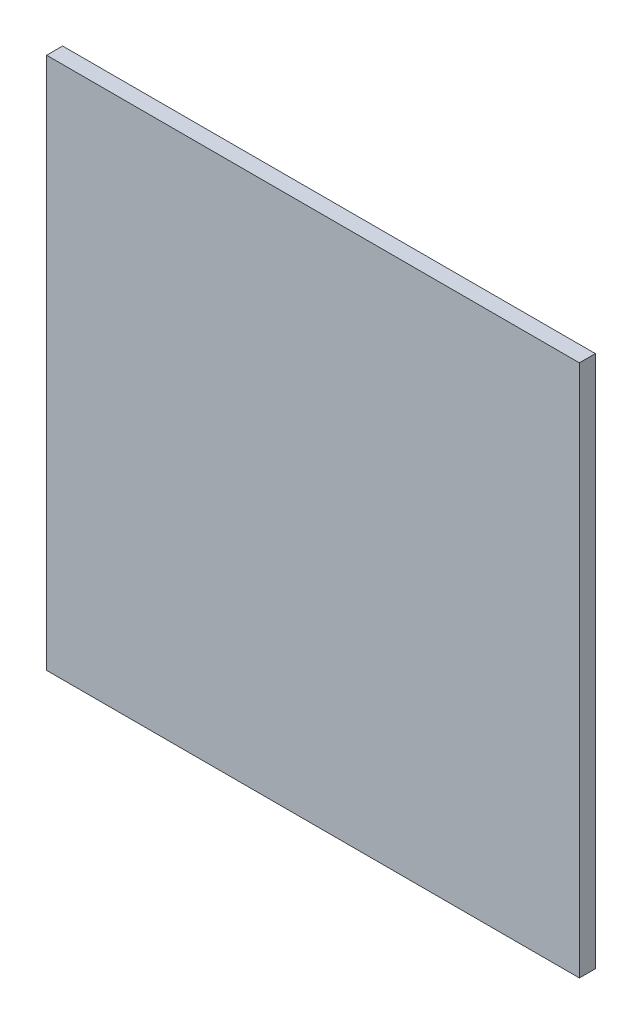
SolidWorks part; units mm, degrees
ref_plane "前视基准面" through (0, 0, 0) normal (0, 0, 1) x (1, 0, 0)
ref_plane "上视基准面" through (0, 0, 0) normal (0, 1, 0) x (1, 0, 0)
ref_plane "右视基准面" through (0, 0, 0) normal (1, 0, 0) x (0, 0, -1)
other "Configuration Table"
sketch "草图2" plane through (0, 0, 0) normal (0, 0, 1) x (1, 0, 0)
  circle A0 centre (0, 0) radius 50
  dimension "D1" = 100
ref_plane "基准面1" through (0, 0, 200) normal (0, 0, 1) x (1, 0, 0)
sketch "草图3" plane through (0, 0, 200) normal (0, 0, 1) x (1, 0, 0)
  circle A0 centre (0, 0) radius 250
  dimension "D1" = 500
loft "放样1" add profiles "草图3", "草图2" connector at (157.2894, 194.3194, 200) connector at (42.3171, 26.632, 0)
sketch "草图4" plane through (0, 0, 200) normal (0, 0, 1) x (1, 0, 0)
  line L0 (0, 250) -> (-250, 250)
  line L1 (-250, 250) -> (-250, -250)
  line L2 (-250, -250) -> (250, -250)
  line L3 (250, -250) -> (250, 250)
  line L4 (250, 250) -> (0, 250)
  circle A0 centre (0, 0) radius 250 construction
  dimension "D1" = 250
  dimension "D2" = 500
  dimension "D3" = 500
extrude "凸台-拉伸1" add sketch "草图4" along normal blind 15
